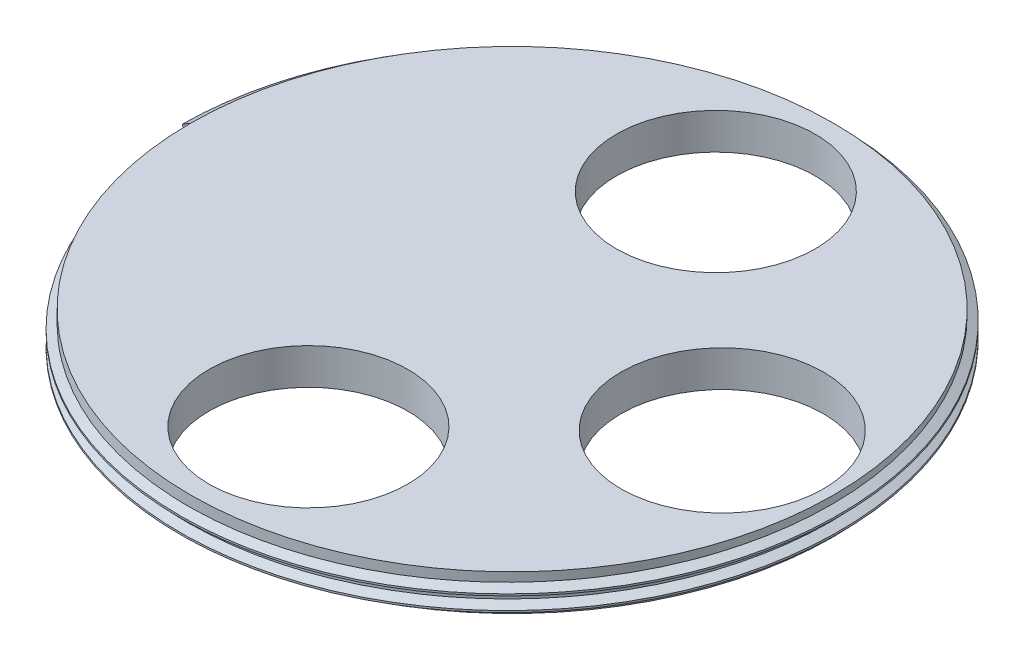
SolidWorks part; units mm, degrees
ref_plane "Front Plane" through (0, 0, 0) normal (0, 0, 1) x (1, 0, 0)
ref_plane "Top Plane" through (0, 0, 0) normal (0, 1, 0) x (1, 0, 0)
ref_plane "Right Plane" through (0, 0, 0) normal (1, 0, 0) x (0, 0, -1)
sketch "Sketch1" plane through (0, 0, 0) normal (0, 1, 0) x (1, 0, 0)
  circle A0 centre (0, 0) radius 44.5
  dimension "D1" = 89
extrude "Boss-Extrude2" add sketch "Sketch1" along normal blind 5
ref_plane "Plane1" through (0, 0, 45) normal (0, 0, 1) x (1, 0, 0)
thread "Thread1" pitch 2 method extrude profile "Thread Profile1" start angle 0, offset 0, length 4, pitch 2, diameter 89
ref_plane "Plane2" through (-44.5, 5, 0) normal (0, 0, 1) x (-1, 0, 0)
sketch "Thread Profile1" plane through (-44.5, 5, 0) normal (0, 0, 1) x (-1, 0, 0)
  line L0 (0, 0) -> (0, 2) construction
  line L1 (0, 0) -> (1.0825, 0.625)
  line L2 (1.0825, 0.625) -> (1.0825, 0.875)
  line L3 (1.0825, 0.875) -> (0, 1.5)
  line L4 (1.0825, 0.75) -> (0, 0.75) construction
  line L11 (0, 0) -> (0, 1.5)
  point P2 (0, 0)
  dimension "Pitch" = 2
  dimension "Profile_Angle" = 60
  dimension "Profile_Land" = 0.25
  dimension "Profile_Height" = 1.0825
sketch "Sketch26" plane through (0, 5, 0) normal (0, 1, 0) x (1, 0, 0)
  circle A0 centre (29.0603, 0) radius 14
  dimension "D1" = 28
extrude "Cut-Extrude1" cut sketch "Sketch26" against normal up to surface and the other way through all up to face at (0, 0, 0)
sketch "Sketch27" plane through (0, 5, 0) normal (0, 1, 0) x (1, 0, 0)
  circle A0 centre (0, -28.1725) radius 13.75
  circle A1 centre (0, 28.1725) radius 13.75
  dimension "D1" = 27.5
  dimension "D2" = 2
extrude "Cut-Extrude2" cut sketch "Sketch27" against normal blind 44.69
